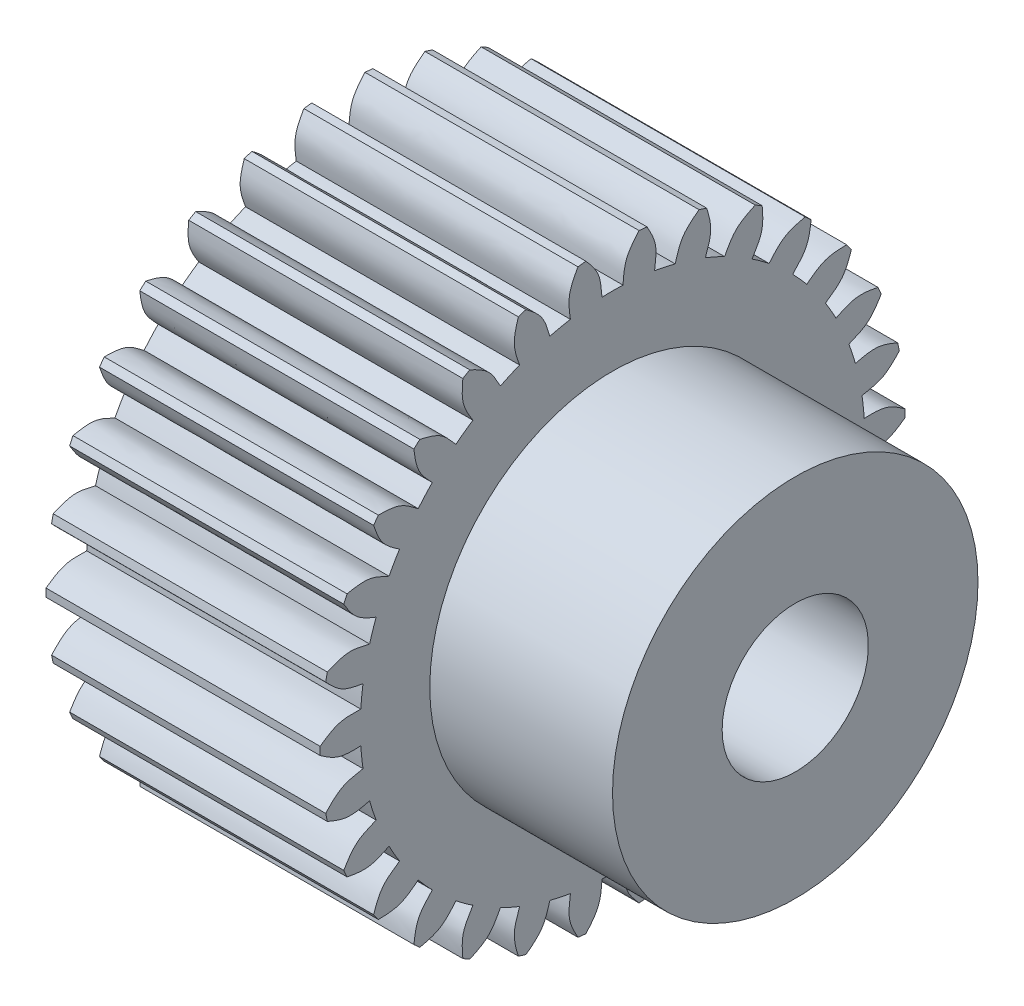
SolidWorks part; units mm, degrees
ref_plane "Front" through (0, 0, 0) normal (0, 0, 1) x (1, 0, 0)
ref_plane "Top" through (0, 0, 0) normal (0, 1, 0) x (1, 0, 0)
ref_plane "Right" through (0, 0, 0) normal (1, 0, 0) x (0, 0, -1)
sketch "Ritning 1" plane through (0, 0, 0) normal (0, 0, 1) x (1, 0, 0)
  line L0 (-12.5, -8) -> (12.5, -8) construction
  line L1 (-12.5, -4) -> (12.5, -4)
  line L2 (12.5, -4) -> (12.5, 2)
  line L3 (12.5, 2) -> (2.5, 2)
  line L4 (2.5, 2) -> (2.5, 8)
  line L5 (2.5, 8) -> (-12.5, 8)
  line L6 (-12.5, 8) -> (-12.5, -4)
  line L7 (-12.5, -4) -> (-12.5, -8) construction
  line L8 (12.5, -8) -> (12.5, -4) construction
  dimension "D1" = 2.5
  dimension "D2" = 12.5
  dimension "D3" = 12.5
  dimension "D4" = 2
  dimension "D5" = 8
  dimension "D7" = 8
revolve "Kugghjulsämne" add sketch "Ritning 1" angle 360 about L0
sketch "Ritning 2" plane through (-12.5, 0, 0) normal (-1, 0, 0) x (0, 0, 1)
  line L0 (0, -8) -> (0, 8) construction
  line L1 (1.4537, 7.9338) -> (0, 9.3875)
  line L2 (-1.4537, 7.9338) -> (0, 9.3875)
  line L3 (0, -8) -> (2.1552, -8) construction
  arc A0 (0.5753, 5.788) -> (-0.5753, 5.788) centre (0, -8) ccw
  circle A1 centre (0, -8) radius 16 construction
  spline S0 degree 3 poles (1.4537, 7.9338) (1.1928, 7.6315) (0.6611, 7.0152) (0.6043, 6.2022) (0.5753, 5.788) knots 0 0 0 0 0.490591 1 1 1 1
  spline S1 degree 3 poles (-1.4537, 7.9338) (-1.1928, 7.6315) (-0.6611, 7.0152) (-0.6043, 6.2022) (-0.5753, 5.788) knots 0 0 0 0 0.490591 1 1 1 1
  dimension "D1" = 13.8
  dimension "D2" = 0.5753
  dimension "D3" = 0.7854
  dimension "D4" = 1.4537
  dimension "D5" = 14.9794
  dimension "D6" = 0.7854
  dimension "D7" = 15.9338
extrude "Kugglucka" cut sketch "Ritning 2" against normal up to surface (15 mm away) up to face at (2.5, -8, 16)
pattern_circular "CirPattern" count 30 over 360 about axis through (-12.5, -8, 0) along (-1, 0, 0) of "Kugglucka"
